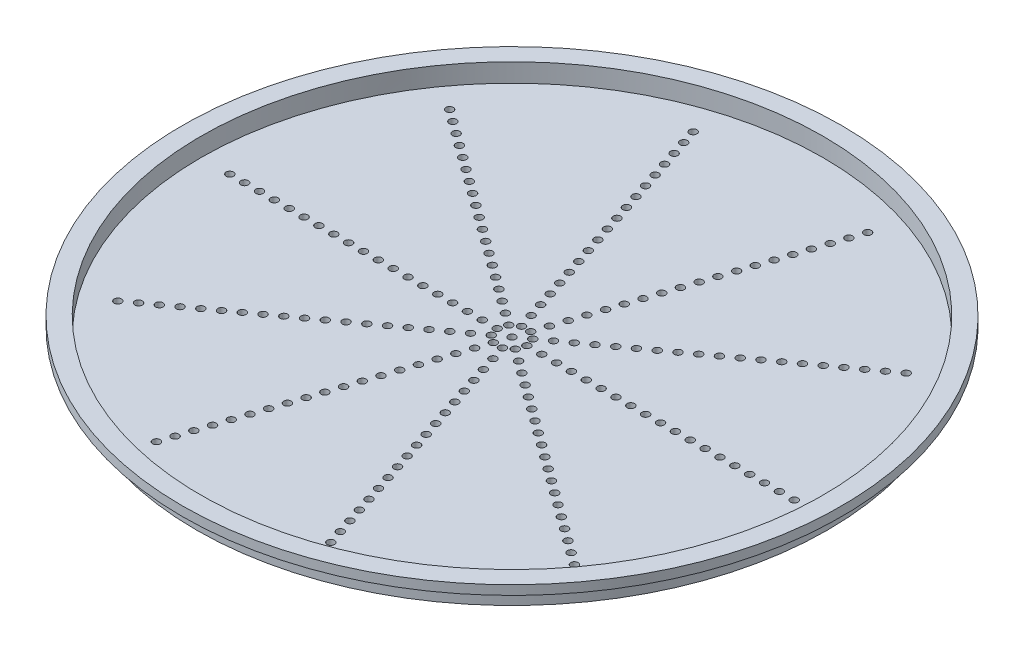
SolidWorks part; units mm, degrees
material "1060 Alloy"
ref_plane "Front Plane" through (0, 0, 0) normal (0, 0, 1) x (1, 0, 0)
ref_plane "Top Plane" through (0, 0, 0) normal (0, 1, 0) x (1, 0, 0)
ref_plane "Right Plane" through (0, 0, 0) normal (1, 0, 0) x (0, 0, -1)
sketch "Croquis1" plane through (0, 0, 0) normal (0, 1, 0) x (1, 0, 0)
  circle A0 centre (0, 0) radius 34
  dimension "D1" = 68
extrude "Saliente-Extruir1" add sketch "Croquis1" along normal blind 1
sketch "Croquis2" plane through (0, 0, 0) normal (0, -1, 0) x (1, 0, 0)
  circle A0 centre (0, 0) radius 33.5
  circle A1 centre (0, 0) radius 34
  dimension "D1" = 67
  dimension "D2" = 68
extrude "Saliente-Extruir3" add sketch "Croquis2" against normal blind 3
sketch "Croquis3" plane through (0, 3, 0) normal (0, 1, 0) x (1, 0, 0)
  circle A0 centre (0, 0) radius 35.5
  circle A1 centre (0, 0) radius 33.5
  dimension "D1" = 71
  dimension "D2" = 67
extrude "Saliente-Extruir4" add sketch "Croquis3" against normal blind 1
sketch "Croquis5" plane through (0, 1, 0) normal (0, 1, 0) x (1, 0, 0)
  circle A0 centre (0, 0) radius 0.4
  circle A1 centre (1.6, 0) radius 0.4
  circle A2 centre (3.2, 0) radius 0.4
  circle A3 centre (4.8, 0) radius 0.4
  circle A4 centre (6.4, 0) radius 0.4
  circle A5 centre (8, 0) radius 0.4
  circle A6 centre (9.6, 0) radius 0.4
  circle A7 centre (11.2, 0) radius 0.4
  circle A8 centre (12.8, 0) radius 0.4
  circle A9 centre (14.4, 0) radius 0.4
  circle A10 centre (16, 0) radius 0.4
  circle A11 centre (17.6, 0) radius 0.4
  circle A12 centre (19.2, 0) radius 0.4
  circle A13 centre (20.8, 0) radius 0.4
  circle A14 centre (22.4, 0) radius 0.4
  circle A15 centre (24, 0) radius 0.4
  circle A16 centre (25.6, 0) radius 0.4
  circle A17 centre (27.2, 0) radius 0.4
  circle A18 centre (28.8, 0) radius 0.4
  circle A19 centre (30.4, 0) radius 0.4
  circle A20 centre (1.2944, -0.9405) radius 0.4
  circle A21 centre (2.5889, -1.8809) radius 0.4
  circle A22 centre (3.8833, -2.8214) radius 0.4
  circle A23 centre (5.1777, -3.7618) radius 0.4
  circle A24 centre (6.4721, -4.7023) radius 0.4
  circle A25 centre (7.7666, -5.6427) radius 0.4
  circle A26 centre (9.061, -6.5832) radius 0.4
  circle A27 centre (10.3554, -7.5237) radius 0.4
  circle A28 centre (11.6498, -8.4641) radius 0.4
  circle A29 centre (12.9443, -9.4046) radius 0.4
  circle A30 centre (14.2387, -10.345) radius 0.4
  circle A31 centre (15.5331, -11.2855) radius 0.4
  circle A32 centre (16.8276, -12.2259) radius 0.4
  circle A33 centre (18.122, -13.1664) radius 0.4
  circle A34 centre (19.4164, -14.1068) radius 0.4
  circle A35 centre (20.7108, -15.0473) radius 0.4
  circle A36 centre (22.0053, -15.9878) radius 0.4
  circle A37 centre (23.2997, -16.9282) radius 0.4
  circle A38 centre (24.5941, -17.8687) radius 0.4
  circle A39 centre (0.4944, -1.5217) radius 0.4
  circle A40 centre (0.9889, -3.0434) radius 0.4
  circle A41 centre (1.4833, -4.5651) radius 0.4
  circle A42 centre (1.9777, -6.0868) radius 0.4
  circle A43 centre (2.4721, -7.6085) radius 0.4
  circle A44 centre (2.9666, -9.1301) radius 0.4
  circle A45 centre (3.461, -10.6518) radius 0.4
  circle A46 centre (3.9554, -12.1735) radius 0.4
  circle A47 centre (4.4498, -13.6952) radius 0.4
  circle A48 centre (4.9443, -15.2169) radius 0.4
  circle A49 centre (5.4387, -16.7386) radius 0.4
  circle A50 centre (5.9331, -18.2603) radius 0.4
  circle A51 centre (6.4276, -19.782) radius 0.4
  circle A52 centre (6.922, -21.3037) radius 0.4
  circle A53 centre (7.4164, -22.8254) radius 0.4
  circle A54 centre (7.9108, -24.347) radius 0.4
  circle A55 centre (8.4053, -25.8687) radius 0.4
  circle A56 centre (8.8997, -27.3904) radius 0.4
  circle A57 centre (9.3941, -28.9121) radius 0.4
  circle A58 centre (-0.4944, -1.5217) radius 0.4
  circle A59 centre (-0.9889, -3.0434) radius 0.4
  circle A60 centre (-1.4833, -4.5651) radius 0.4
  circle A61 centre (-1.9777, -6.0868) radius 0.4
  circle A62 centre (-2.4721, -7.6085) radius 0.4
  circle A63 centre (-2.9666, -9.1301) radius 0.4
  circle A64 centre (-3.461, -10.6518) radius 0.4
  circle A65 centre (-3.9554, -12.1735) radius 0.4
  circle A66 centre (-4.4498, -13.6952) radius 0.4
  circle A67 centre (-4.9443, -15.2169) radius 0.4
  circle A68 centre (-5.4387, -16.7386) radius 0.4
  circle A69 centre (-5.9331, -18.2603) radius 0.4
  circle A70 centre (-6.4276, -19.782) radius 0.4
  circle A71 centre (-6.922, -21.3037) radius 0.4
  circle A72 centre (-7.4164, -22.8254) radius 0.4
  circle A73 centre (-7.9108, -24.347) radius 0.4
  circle A74 centre (-8.4053, -25.8687) radius 0.4
  circle A75 centre (-8.8997, -27.3904) radius 0.4
  circle A76 centre (-9.3941, -28.9121) radius 0.4
  circle A77 centre (-1.2944, -0.9405) radius 0.4
  circle A78 centre (-2.5889, -1.8809) radius 0.4
  circle A79 centre (-3.8833, -2.8214) radius 0.4
  circle A80 centre (-5.1777, -3.7618) radius 0.4
  circle A81 centre (-6.4721, -4.7023) radius 0.4
  circle A82 centre (-7.7666, -5.6427) radius 0.4
  circle A83 centre (-9.061, -6.5832) radius 0.4
  circle A84 centre (-10.3554, -7.5237) radius 0.4
  circle A85 centre (-11.6498, -8.4641) radius 0.4
  circle A86 centre (-12.9443, -9.4046) radius 0.4
  circle A87 centre (-14.2387, -10.345) radius 0.4
  circle A88 centre (-15.5331, -11.2855) radius 0.4
  circle A89 centre (-16.8276, -12.2259) radius 0.4
  circle A90 centre (-18.122, -13.1664) radius 0.4
  circle A91 centre (-19.4164, -14.1068) radius 0.4
  circle A92 centre (-20.7108, -15.0473) radius 0.4
  circle A93 centre (-22.0053, -15.9878) radius 0.4
  circle A94 centre (-23.2997, -16.9282) radius 0.4
  circle A95 centre (-24.5941, -17.8687) radius 0.4
  circle A96 centre (-1.6, 0) radius 0.4
  circle A97 centre (-3.2, 0) radius 0.4
  circle A98 centre (-4.8, 0) radius 0.4
  circle A99 centre (-6.4, 0) radius 0.4
  circle A100 centre (-8, 0) radius 0.4
  circle A101 centre (-9.6, 0) radius 0.4
  circle A102 centre (-11.2, 0) radius 0.4
  circle A103 centre (-12.8, 0) radius 0.4
  circle A104 centre (-14.4, 0) radius 0.4
  circle A105 centre (-16, 0) radius 0.4
  circle A106 centre (-17.6, 0) radius 0.4
  circle A107 centre (-19.2, 0) radius 0.4
  circle A108 centre (-20.8, 0) radius 0.4
  circle A109 centre (-22.4, 0) radius 0.4
  circle A110 centre (-24, 0) radius 0.4
  circle A111 centre (-25.6, 0) radius 0.4
  circle A112 centre (-27.2, 0) radius 0.4
  circle A113 centre (-28.8, 0) radius 0.4
  circle A114 centre (-30.4, 0) radius 0.4
  circle A115 centre (-1.2944, 0.9405) radius 0.4
  circle A116 centre (-2.5889, 1.8809) radius 0.4
  circle A117 centre (-3.8833, 2.8214) radius 0.4
  circle A118 centre (-5.1777, 3.7618) radius 0.4
  circle A119 centre (-6.4721, 4.7023) radius 0.4
  circle A120 centre (-7.7666, 5.6427) radius 0.4
  circle A121 centre (-9.061, 6.5832) radius 0.4
  circle A122 centre (-10.3554, 7.5237) radius 0.4
  circle A123 centre (-11.6498, 8.4641) radius 0.4
  circle A124 centre (-12.9443, 9.4046) radius 0.4
  circle A125 centre (-14.2387, 10.345) radius 0.4
  circle A126 centre (-15.5331, 11.2855) radius 0.4
  circle A127 centre (-16.8276, 12.2259) radius 0.4
  circle A128 centre (-18.122, 13.1664) radius 0.4
  circle A129 centre (-19.4164, 14.1068) radius 0.4
  circle A130 centre (-20.7108, 15.0473) radius 0.4
  circle A131 centre (-22.0053, 15.9878) radius 0.4
  circle A132 centre (-23.2997, 16.9282) radius 0.4
  circle A133 centre (-24.5941, 17.8687) radius 0.4
  circle A134 centre (-0.4944, 1.5217) radius 0.4
  circle A135 centre (-0.9889, 3.0434) radius 0.4
  circle A136 centre (-1.4833, 4.5651) radius 0.4
  circle A137 centre (-1.9777, 6.0868) radius 0.4
  circle A138 centre (-2.4721, 7.6085) radius 0.4
  circle A139 centre (-2.9666, 9.1301) radius 0.4
  circle A140 centre (-3.461, 10.6518) radius 0.4
  circle A141 centre (-3.9554, 12.1735) radius 0.4
  circle A142 centre (-4.4498, 13.6952) radius 0.4
  circle A143 centre (-4.9443, 15.2169) radius 0.4
  circle A144 centre (-5.4387, 16.7386) radius 0.4
  circle A145 centre (-5.9331, 18.2603) radius 0.4
  circle A146 centre (-6.4276, 19.782) radius 0.4
  circle A147 centre (-6.922, 21.3037) radius 0.4
  circle A148 centre (-7.4164, 22.8254) radius 0.4
  circle A149 centre (-7.9108, 24.347) radius 0.4
  circle A150 centre (-8.4053, 25.8687) radius 0.4
  circle A151 centre (-8.8997, 27.3904) radius 0.4
  circle A152 centre (-9.3941, 28.9121) radius 0.4
  circle A153 centre (0.4944, 1.5217) radius 0.4
  circle A154 centre (0.9889, 3.0434) radius 0.4
  circle A155 centre (1.4833, 4.5651) radius 0.4
  circle A156 centre (1.9777, 6.0868) radius 0.4
  circle A157 centre (2.4721, 7.6085) radius 0.4
  circle A158 centre (2.9666, 9.1301) radius 0.4
  circle A159 centre (3.461, 10.6518) radius 0.4
  circle A160 centre (3.9554, 12.1735) radius 0.4
  circle A161 centre (4.4498, 13.6952) radius 0.4
  circle A162 centre (4.9443, 15.2169) radius 0.4
  circle A163 centre (5.4387, 16.7386) radius 0.4
  circle A164 centre (5.9331, 18.2603) radius 0.4
  circle A165 centre (6.4276, 19.782) radius 0.4
  circle A166 centre (6.922, 21.3037) radius 0.4
  circle A167 centre (7.4164, 22.8254) radius 0.4
  circle A168 centre (7.9108, 24.347) radius 0.4
  circle A169 centre (8.4053, 25.8687) radius 0.4
  circle A170 centre (8.8997, 27.3904) radius 0.4
  circle A171 centre (9.3941, 28.9121) radius 0.4
  circle A172 centre (1.2944, 0.9405) radius 0.4
  circle A173 centre (2.5889, 1.8809) radius 0.4
  circle A174 centre (3.8833, 2.8214) radius 0.4
  circle A175 centre (5.1777, 3.7618) radius 0.4
  circle A176 centre (6.4721, 4.7023) radius 0.4
  circle A177 centre (7.7666, 5.6427) radius 0.4
  circle A178 centre (9.061, 6.5832) radius 0.4
  circle A179 centre (10.3554, 7.5237) radius 0.4
  circle A180 centre (11.6498, 8.4641) radius 0.4
  circle A181 centre (12.9443, 9.4046) radius 0.4
  circle A182 centre (14.2387, 10.345) radius 0.4
  circle A183 centre (15.5331, 11.2855) radius 0.4
  circle A184 centre (16.8276, 12.2259) radius 0.4
  circle A185 centre (18.122, 13.1664) radius 0.4
  circle A186 centre (19.4164, 14.1068) radius 0.4
  circle A187 centre (20.7108, 15.0473) radius 0.4
  circle A188 centre (22.0053, 15.9878) radius 0.4
  circle A189 centre (23.2997, 16.9282) radius 0.4
  circle A190 centre (24.5941, 17.8687) radius 0.4
  point P386 (0, 0)
  dimension "D1" = 0.8
  dimension "D2" = 20
  dimension "D3" = 10
extrude "Cortar-Extruir2" cut sketch "Croquis5" against normal blind 6.8
